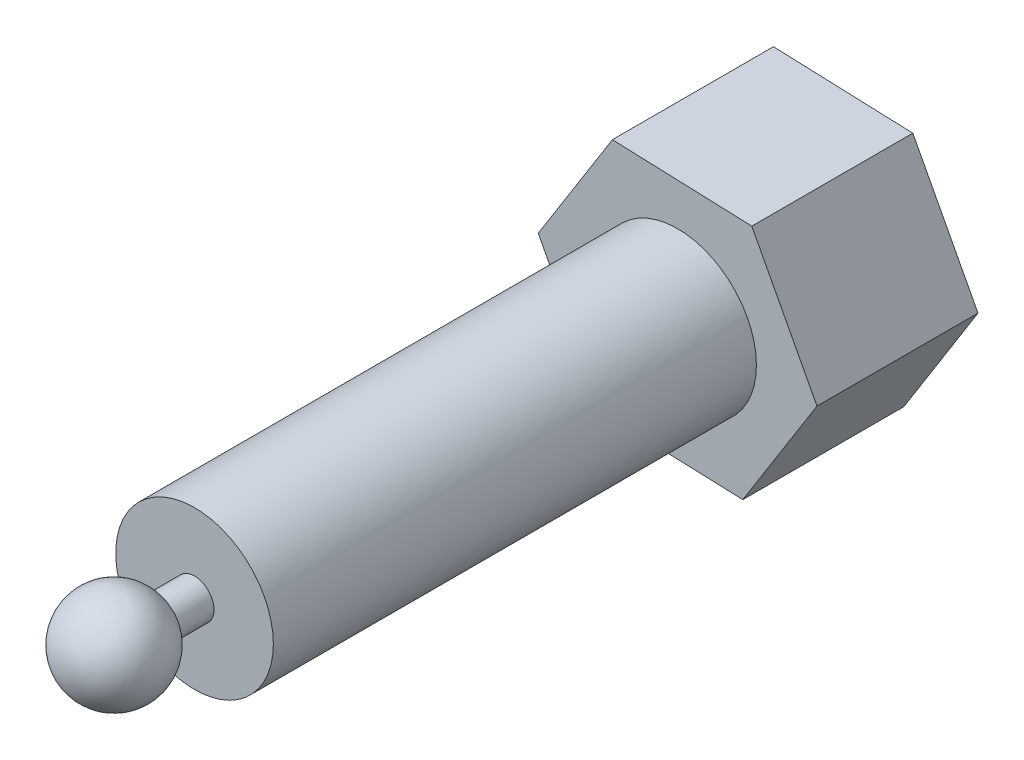
SolidWorks part; units mm, degrees
ref_plane "Plan de face" through (0, 0, 0) normal (0, 0, 1) x (1, 0, 0)
ref_plane "Plan de dessus" through (0, 0, 0) normal (0, 1, 0) x (1, 0, 0)
ref_plane "Plan de droite" through (0, 0, 0) normal (1, 0, 0) x (0, 0, -1)
sketch "Esquisse1" plane through (0, 0, 0) normal (0, 0, 1) x (1, 0, 0)
  line L1 (4.0484, -7.6558) -> (8.6543, -0.3219)
  line L2 (8.6543, -0.3219) -> (4.6059, 7.3339)
  line L3 (4.6059, 7.3339) -> (-4.0484, 7.6558)
  line L4 (-4.0484, 7.6558) -> (-8.6543, 0.3219)
  line L5 (-8.6543, 0.3219) -> (-4.6059, -7.3339)
  line L6 (-4.6059, -7.3339) -> (4.0484, -7.6558)
  circle A0 centre (0, 0) radius 7.5 construction
  point P1 (-7.541, 13.7031)
  point P10 (-4.6059, 7.5)
  point P11 (0, 0)
  dimension "D1" = 15
extrude "Boss.-Extru.1" add sketch "Esquisse1" along normal blind 10
sketch "Esquisse2" plane through (0, 0, 10) normal (0, 0, 1) x (1, 0, 0)
  circle A0 centre (0, 0) radius 4.8941
extrude "Boss.-Extru.2" add sketch "Esquisse1<2>" along normal blind 10
sketch "Esquisse1<2>" plane through (0, 0, 0) normal (0, 0, 1) x (1, 0, 0) same geometry as "Esquisse1"
extrude "Boss.-Extru.3" add sketch "Esquisse2" along normal blind 30 contours A0
sketch "Esquisse3" plane through (0, 0, 40) normal (0, 0, 1) x (1, 0, 0)
  circle A0 centre (0, 0) radius 1.2123
extrude "Boss.-Extru.4" add sketch "Esquisse3" along normal blind 5
sketch "Esquisse4" plane through (0, 0, 45) normal (0, 0, 1) x (1, 0, 0)
  line L0 (0, 0) -> (0, 3) construction
  line L1 (0, 3) -> (0, -3)
  arc A0 (0, -3) -> (0, 3) centre (0, 0) ccw
  point P3 (0, 0)
  point P6 (0, 0)
  dimension "D1" = 6
revolve "Révolution2" add sketch "Esquisse4" angle 360 about L0
